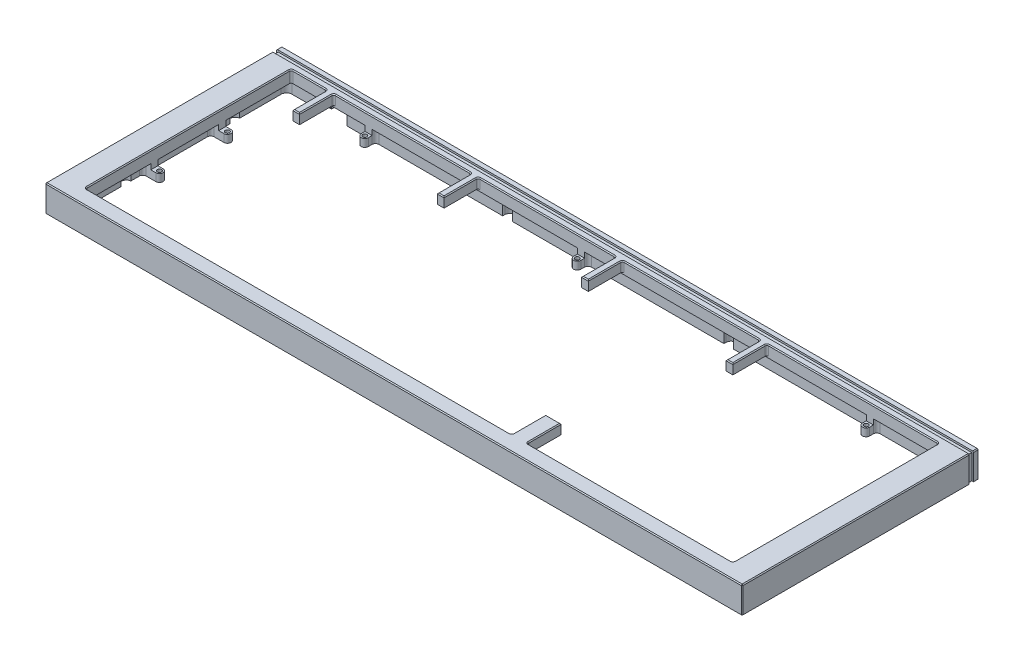
SolidWorks part; units mm, degrees
material "6061-T6 (SS)"
ref_plane "Front Plane" through (0, 0, 0) normal (0, 0, 1) x (1, 0, 0)
ref_plane "Top Plane" through (0, 0, 0) normal (0, 1, 0) x (1, 0, 0)
ref_plane "Right Plane" through (0, 0, 0) normal (1, 0, 0) x (0, 0, -1)
sketch "Sketch1" plane through (0, 0, 0) normal (0, 1, 0) x (1, 0, 0)
  line L1 (0, 0) -> (390.74, 0)
  line L2 (0, 0) -> (0, 132.7)
  line L3 (0, 132.7) -> (390.74, 132.7)
  line L4 (390.74, 0) -> (390.74, 132.7)
  line L5 (13.92, 124) -> (376.82, 124)
  line L6 (13.92, 124) -> (13.92, 8.7)
  line L7 (13.92, 8.7) -> (376.82, 8.7)
  line L8 (376.82, 124) -> (376.82, 8.7)
  point P9 (195.37, 124)
  point P10 (195.37, 132.7)
  point P11 (13.92, 66.35)
  point P12 (0, 66.35)
  dimension "D1" = 362.9
  dimension "D2" = 115.3
  dimension "D3" = 8.7
  dimension "D4" = 13.92
extrude "Main Body" add sketch "Sketch1" along normal blind 14.8
sketch "Sketch2" plane through (0, 0, 0) normal (0, -1, 0) x (1, 0, 0)
  line L0 (390.74, -132.7) -> (0, -132.7) construction
  line L1 (388.74, -130.7) -> (2, -130.7)
  line L2 (388.74, -130.7) -> (388.74, -2)
  line L3 (388.74, -2) -> (2, -2)
  line L4 (2, -130.7) -> (2, -2)
  line L5 (390.74, 0) -> (390.74, -132.7) construction
  point P4 (195.37, -130.7)
  point P7 (195.37, -132.7)
  point P8 (388.74, -66.35)
  point P11 (390.74, -66.35)
  dimension "D1" = 2
  dimension "D2" = 2
extrude "Alignment Guide" cut sketch "Sketch2" against normal blind 1 contours L2 L1 L4 L3
sketch "Sketch3" plane through (0, 14.8, 0) normal (0, 1, 0) x (1, 0, 0)
  line L0 (13.92, 8.7) -> (376.82, 8.7) construction
  line L1 (252.82, 27.8) -> (261.52, 27.8)
  line L2 (252.82, 27.8) -> (252.82, 8.7)
  line L3 (252.82, 8.7) -> (261.52, 8.7)
  line L4 (261.52, 27.8) -> (261.52, 8.7)
  line L5 (376.82, 8.7) -> (376.82, 124) construction
  line L6 (376.82, 124) -> (13.92, 124) construction
  line L7 (33.92, 124) -> (37.72, 124)
  line L8 (33.92, 124) -> (33.92, 104.9)
  line L9 (33.92, 104.9) -> (37.72, 104.9)
  line L10 (37.72, 124) -> (37.72, 104.9)
  line L11 (13.92, 124) -> (13.92, 8.7) construction
  line L12 (114.92, 124) -> (118.72, 124)
  line L13 (114.92, 124) -> (114.92, 104.9)
  line L14 (114.92, 104.9) -> (118.72, 104.9)
  line L15 (118.72, 124) -> (118.72, 104.9)
  line L16 (195.82, 124) -> (199.62, 124)
  line L17 (195.82, 124) -> (195.82, 104.9)
  line L18 (195.82, 104.9) -> (199.62, 104.9)
  line L19 (199.62, 124) -> (199.62, 104.9)
  line L20 (276.82, 124) -> (280.62, 124)
  line L21 (276.82, 124) -> (276.82, 104.9)
  line L22 (276.82, 104.9) -> (280.62, 104.9)
  line L23 (280.62, 124) -> (280.62, 104.9)
  point P8 (257.17, 8.7)
  dimension "D1" = 115.3
  dimension "D2" = 124
  dimension "D3" = 19.1
  dimension "D4" = 3.8
  dimension "D5" = 19.1
  dimension "D6" = 77.2
  dimension "D7" = 77.1
  dimension "D8" = 77.2
  dimension "D9" = 20
extrude "Blockers" add sketch "Sketch3" against normal blind 5.5
fillet "Fillet5" radius 1 14 edges at (280.62, 12.05, -124) (276.82, 12.05, -124) (195.82, 12.05, -124) (199.62, 12.05, -124) (118.72, 12.05, -124) (114.92, 12.05, -124) (33.92, 12.05, -124) (37.72, 12.05, -124) (13.92, 7.9, -124) (13.92, 7.9, -8.7) (252.82, 12.05, -8.7) (261.52, 12.05, -8.7) (376.82, 7.9, -8.7) (376.82, 7.9, -124)
sketch "Sketch4" plane through (0, 1, 0) normal (0, -1, 0) x (1, 0, 0)
  line L0 (0, 0) -> (390.74, 0) construction
  line L1 (381.27, -125.9) -> (9.47, -125.9)
  line L2 (381.27, -125.9) -> (381.27, -6.8)
  line L3 (381.27, -6.8) -> (9.47, -6.8)
  line L4 (9.47, -125.9) -> (9.47, -6.8)
  line L5 (390.74, 0) -> (390.74, -132.7) construction
  point P4 (195.37, -6.8)
  point P7 (195.37, 0)
  point P8 (381.27, -66.35)
  point P11 (390.74, -66.35)
  dimension "D1" = 119.1
  dimension "D2" = 371.8
extrude "PCB Cutout" cut sketch "Sketch4" against normal offset from surface (7.3 mm away) 6.5 up to face at (195.37, 14.8, -66.35)
fillet "Fillet4" radius 3 8 edges at (9.47, 4.65, -6.8) (9.47, 4.65, -125.9) (381.27, 4.65, -125.9) (381.27, 4.65, -6.8) (2, 0.5, -130.7) (2, 0.5, -2) (388.74, 0.5, -2) (388.74, 0.5, -130.7)
sketch "Sketch6" plane through (0, 1, 0) normal (0, -1, 0) x (1, 0, 0)
  line L0 (381.27, -9.8) -> (381.27, -122.9) construction
  line L1 (254.62, -127.1) -> (260.12, -127.1)
  line L2 (254.62, -127.1) -> (254.62, -125.9)
  line L3 (254.62, -125.9) -> (260.12, -125.9)
  line L4 (260.12, -127.1) -> (260.12, -125.9)
  line L5 (12.47, -125.9) -> (378.27, -125.9) construction
  line L11 (378.27, -6.8) -> (12.47, -6.8) construction
  line L16 (260.12, -6.8) -> (254.62, -6.8)
  line L17 (260.12, -6.8) -> (260.12, -4.8)
  line L18 (260.12, -4.8) -> (254.62, -4.8)
  line L19 (254.62, -6.8) -> (254.62, -4.8)
  line L21 (0, 0) -> (390.74, 0) construction
  line L24 (390.74, -66.35) -> (195.37, -66.35) construction
  line L25 (390.74, 0) -> (390.74, -132.7) construction
  line L26 (328.6755, -66.35) -> (328.6755, -130.7) construction
  line L27 (385.74, -130.7) -> (5, -130.7) construction
  line L28 (328.6755, -66.35) -> (328.6755, -8.7) construction
  line L29 (375.82, -8.7) -> (14.92, -8.7) construction
  line L55 (390.74, -132.7) -> (0, -132.7) construction
  line L56 (195.37, -132.7) -> (195.37, 0) construction
  line L57 (136.12, -6.8) -> (136.12, -4.8)
  line L58 (130.62, -4.8) -> (136.12, -4.8)
  line L59 (130.62, -6.8) -> (130.62, -4.8)
  line L60 (130.62, -6.8) -> (136.12, -6.8)
  line L61 (130.62, -127.1) -> (130.62, -125.9)
  line L62 (136.12, -125.9) -> (130.62, -125.9)
  line L63 (136.12, -127.1) -> (136.12, -125.9)
  line L64 (136.12, -127.1) -> (130.62, -127.1)
  circle A0 centre (381.07, -96.85) radius 2.75
  circle A1 centre (381.07, -35.85) radius 2.75
  circle A2 centre (257.37, -4.8) radius 2.75
  circle A3 centre (257.37, -127.1) radius 2.75
  circle A8 centre (133.37, -4.8) radius 2.75
  circle A9 centre (9.67, -35.85) radius 2.75
  circle A10 centre (9.67, -96.85) radius 2.75
  circle A11 centre (133.37, -127.1) radius 2.75
  point P25 (195.37, -66.35)
  point P32 (257.37, -125.9)
  point P33 (257.37, -6.8)
  line M17 (12.47, -6.8) -> (378.27, -6.8)
  line M18 (381.27, -9.8) -> (381.27, -122.9)
  line M19 (378.27, -125.9) -> (12.47, -125.9)
  line M20 (9.47, -122.9) -> (9.47, -9.8)
  dimension "D4" = 5.5
  dimension "D5" = 62
  dimension "D1" = 30.5
  dimension "D2" = 4.8
  dimension "D3" = 30.5
  dimension "D6" = 0.2
  dimension "D7" = 5.6
extrude "PlateTabs" cut sketch "Sketch6" against normal up to surface (7.3 mm away) contours A0 M18 | A1 M18 | A2 L19 M17 | L16 A2 L18 | A2 L17 M17 | L18 A2 | L1 A3 | L1 A3 L3 | A3 L2 M19 | A11 L64 | A11 L64 L62 | A10 M20 | A9 M20 | A8 L58 | A8 L60 L58 | A3 L4 M19 | A8 L59 M17 | L57 A8 M17 | A11 L63 M19 | L61 A11 M19 | A11 | L59 L58 L57 L60 | A3 region at (257.37, 1, -126.5102) region at (136.0381, 1, -126.1969) region at (257.37, 1, -128.2671) region at (254.7019, 1, -126.1969) region at (260.0381, 1, -126.1969) region at (133.37, 1, -126.5102) region at (133.37, 1, -128.2671) region at (130.7019, 1, -126.1969) region at (135.8701, 1, -6.317) region at (259.8701, 1, -6.317) region at (257.37, 1, -5.7445) region at (257.37, 1, -3.6329) region at (254.8699, 1, -6.317) region at (133.37, 1, -5.7445) region at (133.37, 1, -3.6329) region at (130.8699, 1, -6.317) region at (382.3459, 1, -96.85) region at (382.3459, 1, -35.85) region at (8.3941, 1, -96.85) region at (8.3941, 1, -35.85) up to face at (195.37, 8.3, -66.35)
sketch "Sketch9" plane through (0, 0, -132.7) normal (0, 0, -1) x (-1, 0, 0)
  line L1 (-41.8, 0) -> (-29.8, 0)
  line L2 (-41.8, 0) -> (-41.8, 3.2)
  line L3 (-41.8, 3.2) -> (-29.8, 3.2)
  line L4 (-29.8, 0) -> (-29.8, 3.2)
  line L5 (-390.74, 0) -> (0, 0) construction
  line L7 (0, 14.8) -> (0, 0) construction
  point P6 (-35.8, 3.2)
  dimension "D1" = 3.2
  dimension "D3" = 12
  dimension "D4" = 35.8
extrude "USB Cutout" cut sketch "Sketch9" against normal up to surface (8.7 mm away) up to face at (164.89, 11.95, -124)
sketch "Sketch11" plane through (0, 0, -125.9) normal (0, 0, 1) x (1, 0, 0)
  line L0 (130.62, 8.3) -> (12.47, 8.3) construction
  line L1 (43.3, 1) -> (28.3, 1)
  line L2 (43.3, 1) -> (43.3, 8.3)
  line L3 (43.3, 8.3) -> (28.3, 8.3)
  line L4 (28.3, 1) -> (28.3, 8.3)
  line L7 (12.47, 1) -> (29.8, 1) construction
  line L8 (29.8, 3.2) -> (41.8, 3.2) construction
  point P8 (35.8, 1)
  point P18 (35.8, 3.2)
  dimension "D1" = 15
extrude "PCB Clearance" cut sketch "Sketch11" against normal blind 3.9
fillet "Fillet7" radius 2.5 2 edges at (28.3, 4.65, -129.8) (43.3, 4.65, -129.8)
sketch "Sketch12" plane through (0, 8.3, 0) normal (0, -1, 0) x (1, 0, 0)
  line L0 (195.37, -132.7) -> (195.37, 0) construction
  line L2 (14.92, -124) -> (375.82, -124) construction
  line L3 (0, 0) -> (390.74, 0) construction
  line L5 (390.74, -132.7) -> (41.8, -132.7) construction
  line L8 (376.82, -123) -> (376.82, -9.7) construction
  arc A0 (381.27, -38.5927) -> (381.27, -33.1073) centre (381.07, -35.85) ccw construction
  arc A1 (381.27, -99.5927) -> (381.27, -94.1073) centre (381.07, -96.85) ccw construction
  point P0 (257.37, -127.1)
  point P1 (381.42, -96.85)
  point P2 (381.42, -35.85)
  point P3 (257.37, -4.85)
  point P7 (195.37, -66.35)
  point P8 (133.37, -4.85)
  point P10 (9.32, -35.85)
  point P14 (9.32, -96.85)
  point P16 (133.37, -127.1)
  point P34 (383.82, -35.85)
  point P39 (383.82, -96.85)
  dimension "D1" = 3.1
  dimension "D2" = 61.5
  dimension "D3" = 4.6
  dimension "D4" = 62
chamfer "Chamfer1" distance 0.5 46 edges at (14.2129, 14.8, -8.9929) (133.37, 14.8, -8.7) (252.5271, 14.8, -8.9929) (252.82, 14.8, -18.75) (257.17, 14.8, -27.8) (261.52, 14.8, -18.75) (261.8129, 14.8, -8.9929) (319.17, 14.8, -8.7) (376.5271, 14.8, -8.9929) (376.82, 14.8, -66.35) (376.5271, 14.8, -123.7071) (328.72, 14.8, -124) (280.9129, 14.8, -123.7071) (280.62, 14.8, -113.95) (278.72, 14.8, -104.9) (276.82, 14.8, -113.95) (276.5271, 14.8, -123.7071) (238.22, 14.8, -124) (199.9129, 14.8, -123.7071) (199.62, 14.8, -113.95) (197.72, 14.8, -104.9) (195.82, 14.8, -113.95) (195.5271, 14.8, -123.7071) (157.27, 14.8, -124) (119.0129, 14.8, -123.7071) (118.72, 14.8, -113.95) (116.82, 14.8, -104.9) (114.92, 14.8, -113.95) (114.6271, 14.8, -123.7071) (76.32, 14.8, -124) (38.0129, 14.8, -123.7071) (37.72, 14.8, -113.95) (35.82, 14.8, -104.9) (33.92, 14.8, -113.95) (33.6271, 14.8, -123.7071) (23.92, 14.8, -124) (14.2129, 14.8, -123.7071) (13.92, 14.8, -66.35) (195.37, 14.8, -132.7) (390.74, 14.8, -66.35) (195.37, 14.8, 0) (0, 14.8, -66.35) (390.74, 7.4, -132.7) (390.74, 7.4, 0) (0, 7.4, -132.7) (0, 7.4, 0)
chamfer "Chamfer2" distance 0.1 5 edges at (390.74, 0, -66.35) (195.37, 0, 0) (0, 0, -66.35) (15.15, 0, -132.7) (216.02, 0, -132.7)
sketch "Sketch27" plane through (0, 14.8, 0) normal (0, 1, 0) x (1, 0, 0)
  line L0 (0, 0.5) -> (0, 132.2) construction
  line L1 (0, 129.7) -> (390.74, 129.7)
  line L2 (0, 129.7) -> (0, 127.2)
  line L3 (0, 127.2) -> (390.74, 127.2)
  line L4 (390.74, 129.7) -> (390.74, 127.2)
  line L5 (390.74, 132.2) -> (390.74, 0.5) construction
  line L8 (0.5, 132.7) -> (390.24, 132.7) construction
  dimension "D1" = 2.5
  dimension "D2" = 3
extrude "Cut-Extrude11" cut sketch "Sketch27" against normal blind 1
sketch "Sketch28" plane through (0, 13.8, 0) normal (0, 1, 0) x (1, 0, 0)
  line L1 (0, 129.7) -> (1, 129.7)
  line L2 (0, 129.7) -> (0, 127.2)
  line L3 (0, 127.2) -> (1, 127.2)
  line L4 (1, 129.7) -> (1, 127.2)
  line L5 (389.74, 129.7) -> (390.74, 129.7)
  line L6 (389.74, 129.7) -> (389.74, 127.2)
  line L7 (389.74, 127.2) -> (390.74, 127.2)
  line L8 (390.74, 129.7) -> (390.74, 127.2)
  line L9 (390.74, 129.7) -> (0, 129.7) construction
  line L10 (0, 127.2) -> (390.74, 127.2) construction
  dimension "D1" = 1
  dimension "D2" = 1
extrude "Cut-Extrude12" cut sketch "Sketch28" against normal through all
sketch "Sketch21" [suppressed] plane through (0, 14.8, 0) normal (0, 1, 0) x (1, 0, 0)
  line L0 (0.5, 132.7) -> (390.24, 132.7) construction
  line L1 (382.53, 132.7) -> (385.03, 132.7)
  line L2 (382.53, 132.7) -> (382.53, 72.7)
  line L3 (382.53, 72.7) -> (385.03, 72.7)
  line L4 (385.03, 132.7) -> (385.03, 72.7)
  line L5 (390.74, 132.2) -> (390.74, 129.7) construction
  line L6 (390.74, 129.1) -> (294.74, 129.1)
  line L7 (390.74, 129.1) -> (390.74, 127.6)
  line L8 (390.74, 127.6) -> (294.74, 127.6)
  line L9 (294.74, 129.1) -> (294.74, 127.6)
  line L10 (362.9081, 132.2) -> (362.9081, 124.5) construction
  line L11 (390.24, 132.2) -> (0.5, 132.2) construction
  line L12 (281.62, 124.5) -> (375.82, 124.5) construction
  line L13 (365.5702, 129.1) -> (365.5702, 127.6) construction
  line L14 (377.32, 119.5259) -> (390.24, 119.5259) construction
  line L15 (377.32, 123) -> (377.32, 9.7) construction
  line L16 (390.24, 0.5) -> (390.24, 127.2) construction
  line L17 (382.53, 116.0504) -> (385.03, 116.0504) construction
  point P28 (383.78, 116.0504)
  point P29 (383.78, 119.5259)
  point P30 (365.5702, 128.35)
  point P31 (362.9081, 128.35)
  dimension "D1" = 2.5
  dimension "D2" = 1.5
  dimension "D3" = 60
  dimension "D4" = 96
extrude "Cut-Extrude5" [suppressed] cut sketch "Sketch21" against normal blind 1 contours L4 L3 L2 L1 | L8 L9 L6 L7
sketch "Sketch23" [suppressed] plane through (390.74, 0, 0) normal (1, 0, 0) x (0, 0, -1)
  line L0 (129.1, 13.8) -> (129.1, 14.3) construction
  line L1 (127.6, 13.8) -> (129.1, 13.8)
  line L2 (127.6, 13.8) -> (127.6, 0)
  line L3 (127.6, 0) -> (129.1, 0)
  line L4 (129.1, 13.8) -> (129.1, 0)
extrude "Cut-Extrude6" [suppressed] cut sketch "Sketch23" against normal blind 1
sketch "Sketch19" plane through (0, 14.8, 0) normal (0, 1, 0) x (1, 0, 0)
  line L0 (0.5, 132.7) -> (390.24, 132.7) construction
  line L1 (5.46, 132.7) -> (8.46, 132.7)
  line L2 (5.46, 132.7) -> (5.46, 0)
  line L3 (5.46, 0) -> (8.46, 0)
  line L4 (8.46, 132.7) -> (8.46, 0)
  line L7 (382.28, 132.7) -> (385.28, 132.7)
  line L8 (382.28, 132.7) -> (382.28, 0)
  line L9 (382.28, 0) -> (385.28, 0)
  line L10 (385.28, 132.7) -> (385.28, 0)
  line L11 (390.24, 0) -> (0.5, 0) construction
  line L12 (377.32, 110.209) -> (390.24, 110.209) construction
  line L13 (377.32, 123) -> (377.32, 9.7) construction
  line L14 (390.24, 0.5) -> (390.24, 127.2) construction
  line L15 (382.28, 106.8719) -> (385.28, 106.8719) construction
  line L16 (0.5, 106.8719) -> (13.42, 106.8719) construction
  line L17 (0.5, 132.2) -> (0.5, 129.7) construction
  line L18 (13.42, 9.7) -> (13.42, 123) construction
  line L19 (5.46, 102.7297) -> (8.46, 102.7297) construction
  point P12 (383.78, 106.8719)
  point P14 (383.78, 110.209)
  point P30 (6.96, 102.7297)
  point P31 (6.96, 106.8719)
  dimension "D1" = 3
  dimension "D2" = 3
extrude "Cut-Extrude3" [suppressed] cut sketch "Sketch19" against normal blind 1
sketch "Sketch17" plane through (0, 14.8, 0) normal (0, 1, 0) x (1, 0, 0)
  line L0 (390.24, 0.5) -> (390.24, 127.2) construction
  line L1 (5.71, 129.6) -> (385.03, 129.6)
  line L2 (5.71, 129.6) -> (5.71, -1.9)
  line L3 (5.71, -1.9) -> (385.03, -1.9)
  line L4 (385.03, 129.6) -> (385.03, -1.9)
  line L5 (8.21, 127.1) -> (382.53, 127.1)
  line L6 (8.21, 127.1) -> (8.21, 0.6)
  line L7 (8.21, 0.6) -> (382.53, 0.6)
  line L8 (382.53, 127.1) -> (382.53, 0.6)
  line L9 (390.24, 132.2) -> (0.5, 132.2) construction
  line L10 (21.2533, 132.2) -> (21.2533, 124.5) construction
  line L11 (14.92, 124.5) -> (32.92, 124.5) construction
  line L12 (25.2757, 129.6) -> (25.2757, 127.1) construction
  line L13 (0.5, 116.1326) -> (13.42, 116.1326) construction
  line L14 (0.5, 132.2) -> (0.5, 129.7) construction
  line L15 (13.42, 9.7) -> (13.42, 123) construction
  line L16 (5.71, 120.1548) -> (8.21, 120.1548) construction
  point P8 (382.53, 63.85)
  point P9 (385.03, 63.85)
  point P12 (390.24, 63.85)
  point P13 (195.37, 129.6)
  point P14 (195.37, 127.1)
  point P17 (195.37, 132.2)
  point P24 (25.2757, 128.35)
  point P25 (21.2533, 128.35)
  point P34 (6.96, 116.1326)
  point P35 (6.96, 120.1548)
  dimension "D1" = 2.5
  dimension "D2" = 2.5
extrude "Cut-Extrude1" [suppressed] cut sketch "Sketch17" against normal blind 1
hole_wizard "M2x0.4 Tapped Hole1" positions "3DSketch3" profile "Sketch31" tap size "M2x0.4" standard "ANSI Metric"
sketch3d "3DSketch3"
  point P0 (381.42, 8.3, -96.85)
  point P3 (381.42, 8.3, -35.85)
  point P7 (257.37, 8.3, -4.85)
  point P10 (133.37, 8.3, -4.85)
  point P13 (9.32, 8.3, -35.85)
  point P16 (9.32, 8.3, -96.85)
  point P19 (133.37, 8.3, -127.1)
  point P22 (257.37, 8.3, -127.1)
sketch "Sketch31" plane through (381.42, 8.3, -96.85) normal (1, 0, 0) x (0, 0, -1)
  line L0 (0, 0) -> (0, 4.4807)
  line L1 (0, 4.4807) -> (0.8, 4)
  line L2 (0.8, 4) -> (0.8, 0)
  line L5 (0.8, 0) -> (0, 0)
  line L10 (0, 4.4807) -> (-0.8, 4) construction
  line L11 (0, -6.35) -> (0, 107.95) construction
  dimension "Tap Drill Dia." = 1.6
  dimension "Tap Drill Depth" = 4
  dimension "Drill Angle" = 118
cosmetic thread "Hole Thread19" parameters "D1"=4, "D2"=2
cosmetic thread "Hole Thread20" parameters "D1"=4, "D2"=2
cosmetic thread "Hole Thread21" parameters "D1"=4, "D2"=2
cosmetic thread "Hole Thread22" parameters "D1"=4, "D2"=2
cosmetic thread "Hole Thread23" parameters "D1"=4, "D2"=2
cosmetic thread "Hole Thread24" parameters "D1"=4, "D2"=2
cosmetic thread "Hole Thread25" parameters "D1"=4, "D2"=2
cosmetic thread "Hole Thread26" parameters "D1"=4, "D2"=2
fillet "Fillet8" radius 0.1 9 edges at (213.77, 0, -130.7) (387.8613, 0, -129.8213) (17.4, 0, -130.7) (2.8787, 0, -129.8213) (2, 0, -66.35) (2.8787, 0, -2.8787) (195.37, 0, -2) (387.8613, 0, -2.8787) (388.74, 0, -66.35)
sketch "Sketch32" plane through (0, 1, 0) normal (0, -1, 0) x (1, 0, 0)
  line L1 (0, -127.2) -> (0, -0.5) construction
  line L3 (378.27, -125.9) -> (260.12, -125.9) construction
  line L4 (340.3, -121.9) -> (336.3, -121.9)
  line L5 (340.3, -121.9) -> (340.3, -125.9)
  line L6 (340.3, -125.9) -> (336.3, -125.9)
  line L7 (336.3, -121.9) -> (336.3, -125.9)
  line L8 (254.62, -125.9) -> (136.12, -125.9) construction
  line L9 (178.4, -121.9) -> (174.4, -121.9)
  line L10 (178.4, -121.9) -> (178.4, -125.9)
  line L11 (178.4, -125.9) -> (174.4, -125.9)
  line L12 (174.4, -121.9) -> (174.4, -125.9)
  line L13 (43.3, -125.9) -> (130.62, -125.9) construction
  line L14 (59.3, -121.9) -> (55.3, -121.9)
  line L15 (59.3, -121.9) -> (59.3, -125.9)
  line L16 (59.3, -125.9) -> (55.3, -125.9)
  line L17 (55.3, -121.9) -> (55.3, -125.9)
  line L18 (9.47, -38.5927) -> (9.47, -94.1073) construction
  line L19 (16.8, -83.4) -> (9.47, -83.4)
  line L20 (16.8, -83.4) -> (16.8, -87.4)
  line L21 (16.8, -87.4) -> (9.47, -87.4)
  line L22 (9.47, -83.4) -> (9.47, -87.4)
  line L23 (12.47, -6.8) -> (130.62, -6.8) construction
  line L24 (16.8, -45.3) -> (9.47, -45.3)
  line L25 (16.8, -45.3) -> (16.8, -49.3)
  line L26 (16.8, -49.3) -> (9.47, -49.3)
  line L27 (9.47, -45.3) -> (9.47, -49.3)
  line L28 (87.9, -11.6) -> (83.9, -11.6)
  line L29 (87.9, -11.6) -> (87.9, -6.8)
  line L30 (87.9, -6.8) -> (83.9, -6.8)
  line L31 (83.9, -11.6) -> (83.9, -6.8)
  line L32 (254.62, -6.8) -> (136.12, -6.8) construction
  line L33 (158.5, -11.6) -> (154.5, -11.6)
  line L34 (158.5, -11.6) -> (158.5, -6.8)
  line L35 (158.5, -6.8) -> (154.5, -6.8)
  line L36 (154.5, -11.6) -> (154.5, -6.8)
  line L37 (378.27, -6.8) -> (260.12, -6.8) construction
  line L38 (302.2, -11.6) -> (298.2, -11.6)
  line L39 (302.2, -11.6) -> (302.2, -6.8)
  line L40 (302.2, -6.8) -> (298.2, -6.8)
  line L41 (298.2, -11.6) -> (298.2, -6.8)
  line L42 (195.37, 0) -> (195.37, -132.6) construction
  line L43 (0.5, 0) -> (390.24, 0) construction
  line L44 (381.27, -45.3) -> (381.27, -49.3)
  line L45 (373.94, -49.3) -> (381.27, -49.3)
  line L46 (373.94, -45.3) -> (373.94, -49.3)
  line L47 (373.94, -45.3) -> (381.27, -45.3)
  line L48 (381.27, -83.4) -> (381.27, -87.4)
  line L49 (373.94, -87.4) -> (381.27, -87.4)
  line L50 (373.94, -83.4) -> (373.94, -87.4)
  line L51 (373.94, -83.4) -> (381.27, -83.4)
  line L52 (41.8, -132.6) -> (390.34, -132.6) construction
  line L53 (29.8, -132.7) -> (41.8, -132.7) construction
  circle A0 centre (338.3, -121.9) radius 2
  circle A1 centre (176.4, -121.9) radius 2
  circle A2 centre (57.3, -121.9) radius 2
  circle A3 centre (16.8, -85.4) radius 2
  circle A4 centre (16.8, -47.3) radius 2
  circle A5 centre (85.9, -11.6) radius 2
  circle A6 centre (156.5, -11.6) radius 2
  circle A7 centre (300.2, -11.6) radius 2
  circle A8 centre (373.94, -47.3) radius 2
  circle A9 centre (373.94, -85.4) radius 2
  dimension "D1" = 4
  dimension "D2" = 10.8
  dimension "D3" = 57.3
  dimension "D4" = 119.1
  dimension "D5" = 161.9
  dimension "D6" = 36.5
  dimension "D7" = 38.1
  dimension "D8" = 28.6
  dimension "D9" = 70.6
  dimension "D10" = 143.7
  dimension "D11" = 40.5
  dimension "D12" = 110.3
extrude "Boss-Extrude1" add sketch "Sketch32" against normal offset from surface (4.3 mm away) 3 contours A1 | L12 L11 L10 L9 | A0 | L5 L6 L7 L4 | A9 | L51 L48 L49 L50 | L47 L44 L45 L46 | A8 | L41 L40 L39 L38 | A7 | A6 | L36 L35 L34 L33 | A5 | L31 L30 L29 L28 | A4 | L26 L27 L24 L25 | A3 | L19 L22 L21 L20 | A2 | L15 L16 L17 L14 up to face at (381.42, 8.3, -97.65)
sketch "Sketch33" plane through (0, 8.3, 0) normal (0, -1, 0) x (1, 0, 0)
  line L0 (373.94, -83.4) -> (381.27, -83.4) construction
  line L1 (381.27, -87.4) -> (376.82, -87.4)
  line L2 (381.27, -87.4) -> (381.27, -83.4)
  line L3 (381.27, -83.4) -> (376.82, -83.4)
  line L4 (376.82, -87.4) -> (376.82, -83.4)
  line L5 (376.82, -123) -> (376.82, -9.7) construction
  line L6 (373.94, -45.3) -> (381.27, -45.3) construction
  line L7 (381.27, -49.3) -> (376.82, -49.3)
  line L8 (381.27, -49.3) -> (381.27, -45.3)
  line L9 (381.27, -45.3) -> (376.82, -45.3)
  line L10 (376.82, -49.3) -> (376.82, -45.3)
  line L11 (375.82, -8.7) -> (14.92, -8.7) construction
  line L12 (302.2, -6.8) -> (298.2, -6.8)
  line L13 (302.2, -6.8) -> (302.2, -8.7)
  line L14 (302.2, -8.7) -> (298.2, -8.7)
  line L15 (298.2, -6.8) -> (298.2, -8.7)
  line L16 (298.2, -11.6) -> (298.2, -6.8) construction
  line L17 (154.5, -11.6) -> (154.5, -6.8) construction
  line L18 (158.5, -6.8) -> (154.5, -6.8)
  line L19 (158.5, -6.8) -> (158.5, -8.7)
  line L20 (158.5, -8.7) -> (154.5, -8.7)
  line L21 (154.5, -6.8) -> (154.5, -8.7)
  line L22 (83.9, -11.6) -> (83.9, -6.8) construction
  line L23 (87.9, -6.8) -> (83.9, -6.8)
  line L24 (87.9, -6.8) -> (87.9, -8.7)
  line L25 (87.9, -8.7) -> (83.9, -8.7)
  line L26 (83.9, -6.8) -> (83.9, -8.7)
  line L27 (16.8, -49.3) -> (9.47, -49.3) construction
  line L28 (9.47, -45.3) -> (13.92, -45.3)
  line L29 (9.47, -45.3) -> (9.47, -49.3)
  line L30 (9.47, -49.3) -> (13.92, -49.3)
  line L31 (13.92, -45.3) -> (13.92, -49.3)
  line L32 (13.92, -9.7) -> (13.92, -123) construction
  line L33 (16.8, -87.4) -> (9.47, -87.4) construction
  line L34 (9.47, -83.4) -> (13.92, -83.4)
  line L35 (9.47, -83.4) -> (9.47, -87.4)
  line L36 (9.47, -87.4) -> (13.92, -87.4)
  line L37 (13.92, -83.4) -> (13.92, -87.4)
  line L38 (59.3, -121.9) -> (59.3, -125.9) construction
  line L39 (55.3, -125.9) -> (59.3, -125.9)
  line L40 (55.3, -125.9) -> (55.3, -124)
  line L41 (55.3, -124) -> (59.3, -124)
  line L42 (59.3, -125.9) -> (59.3, -124)
  line L43 (14.92, -124) -> (375.82, -124) construction
  line L44 (178.4, -121.9) -> (178.4, -125.9) construction
  line L45 (174.4, -125.9) -> (178.4, -125.9)
  line L46 (174.4, -125.9) -> (174.4, -124)
  line L47 (174.4, -124) -> (178.4, -124)
  line L48 (178.4, -125.9) -> (178.4, -124)
  line L49 (340.3, -121.9) -> (340.3, -125.9) construction
  line L50 (336.3, -125.9) -> (340.3, -125.9)
  line L51 (336.3, -125.9) -> (336.3, -124)
  line L52 (336.3, -124) -> (340.3, -124)
  line L53 (340.3, -125.9) -> (340.3, -124)
extrude "Boss-Extrude2" add sketch "Sketch33" along normal up to surface (3 mm away) up to face at (338.3, 5.3, -123.4)
fillet "Fillet9" radius 1.9 19 edges at (340.3, 4.65, -125.9) (336.3, 4.65, -125.9) (174.4, 4.65, -125.9) (178.4, 4.65, -125.9) (59.3, 4.65, -125.9) (55.3, 4.65, -125.9) (9.47, 4.65, -87.4) (9.47, 4.65, -83.4) (9.47, 4.65, -45.3) (9.47, 4.65, -49.3) (87.9, 4.65, -6.8) (83.9, 4.65, -6.8) (154.5, 4.65, -6.8) (158.5, 4.65, -6.8) (302.2, 4.65, -6.8) (298.2, 4.65, -6.8) (381.27, 4.65, -45.3) (381.27, 4.65, -49.3) (381.27, 4.65, -87.4)
sketch "Sketch34" plane through (0, 5.3, 0) normal (0, 1, 0) x (1, 0, 0)
  point P0 (16.8, 47.3)
  point P1 (16.8, 85.4)
  point P3 (85.9, 11.6)
  point P5 (156.5, 11.6)
  point P7 (300.2, 11.6)
  point P9 (373.94, 47.3)
  point P11 (373.94, 85.4)
  point P13 (338.3, 121.9)
  point P15 (176.4, 121.9)
  point P17 (57.3, 121.9)
hole_wizard "M2 Clearance Hole1" positions "3DSketch4" profile "Sketch35" hole size "M2" standard "ANSI Metric" end condition through all
sketch3d "3DSketch4"
  point P0 (57.3, 5.3, -121.9)
  point P3 (16.8, 5.3, -85.4)
  point P6 (16.8, 5.3, -47.3)
  point P9 (85.9, 5.3, -11.6)
  point P12 (156.5, 5.3, -11.6)
  point P15 (300.2, 5.3, -11.6)
  point P18 (373.94, 5.3, -47.3)
  point P21 (373.94, 5.3, -85.4)
  point P24 (338.3, 5.3, -121.9)
  point P27 (176.4, 5.3, -121.9)
sketch "Sketch35" plane through (57.3, 5.3, -121.9) normal (1, 0, 0) x (0, 0, 1)
  line L0 (0, 0) -> (0, 5.3)
  line L1 (0, 5.3) -> (1.2, 5.3)
  line L2 (1.2, 5.3) -> (1.2, 0)
  line L5 (1.2, 0) -> (0, 0)
  line L11 (0, -6.35) -> (0, 107.95) construction
  dimension "Thru Hole Dia." = 2.4
  dimension "Thru Hole Depth" = 5.3
